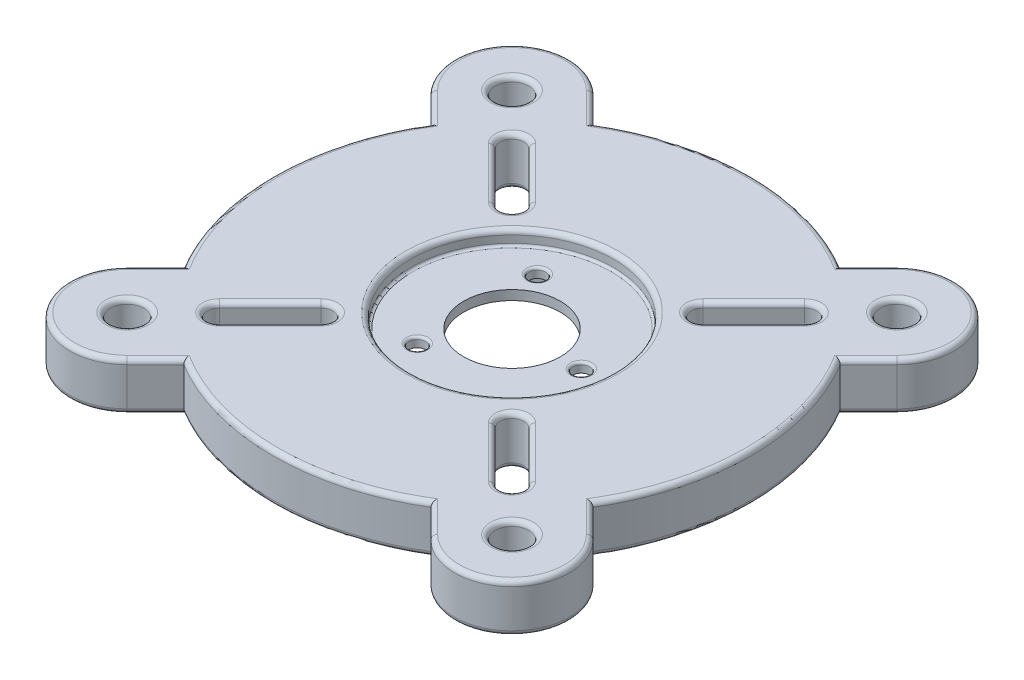
SolidWorks part; units mm, degrees
ref_plane "Front Plane" through (0, 0, 0) normal (0, 0, 1) x (1, 0, 0)
ref_plane "Top Plane" through (0, 0, 0) normal (0, 1, 0) x (1, 0, 0)
ref_plane "Right Plane" through (0, 0, 0) normal (1, 0, 0) x (0, 0, -1)
sketch "Sketch1" plane through (0, 0, 0) normal (0, 1, 0) x (1, 0, 0)
  line L0 (0, 0) -> (0, 28636.0271) construction
  line L1 (0, 0) -> (-28636.0271, 0) construction
  line L2 (-40.2487, -40.2487) -> (40.2487, 40.2487) construction
  line L3 (-48.734, -31.7635) -> (31.7635, 48.734)
  line L4 (-31.7635, -48.734) -> (48.734, 31.7635)
  line L5 (-40.2042, 40.2042) -> (40.2042, -40.2042) construction
  line L6 (-31.7189, 48.6895) -> (48.6895, -31.7189)
  line L7 (-48.6895, 31.7189) -> (31.7189, -48.6895)
  line L8 (20, 20) -> (30.6066, 30.6066) construction
  line L9 (18.2322, 21.7678) -> (28.8388, 32.3744)
  line L10 (21.7678, 18.2322) -> (32.3744, 28.8388)
  line L11 (20, -20) -> (30.6066, -30.6066) construction
  line L12 (21.7678, -18.2322) -> (32.3744, -28.8388)
  line L13 (18.2322, -21.7678) -> (28.8388, -32.3744)
  line L14 (-20, -20) -> (-30.6066, -30.6066) construction
  line L15 (-18.2322, -21.7678) -> (-28.8388, -32.3744)
  line L16 (-21.7678, -18.2322) -> (-32.3744, -28.8388)
  line L17 (-20, 20) -> (-30.6066, 30.6066) construction
  line L18 (-21.7678, 18.2322) -> (-32.3744, 28.8388)
  line L19 (-18.2322, 21.7678) -> (-28.8388, 32.3744)
  circle A0 centre (0, 0) radius 50
  arc A1 (-48.734, -31.7635) -> (-31.7635, -48.734) centre (-40.2487, -40.2487) ccw
  arc A2 (48.734, 31.7635) -> (31.7635, 48.734) centre (40.2487, 40.2487) ccw
  arc A3 (-31.7189, 48.6895) -> (-48.6895, 31.7189) centre (-40.2042, 40.2042) ccw
  arc A4 (31.7189, -48.6895) -> (48.6895, -31.7189) centre (40.2042, -40.2042) ccw
  arc A5 (48.734, 31.7635) -> (46.2093, 19.0972) centre (56.9581, 23.5394) ccw
  arc A6 (31.8511, 48.8208) -> (18.9141, 46.2845) centre (23.4535, 57.3928) cw
  circle A7 centre (40.2487, 40.2487) radius 3.5
  arc A8 (18.2322, 21.7678) -> (21.7678, 18.2322) centre (20, 20) ccw
  arc A9 (32.3744, 28.8388) -> (28.8388, 32.3744) centre (30.6066, 30.6066) ccw
  arc A10 (31.7635, -48.734) -> (19.0972, -46.2093) centre (23.5394, -56.9581) ccw
  circle A11 centre (40.2487, -40.2487) radius 3.5
  arc A12 (48.8208, -31.8511) -> (46.2845, -18.9141) centre (57.3928, -23.4535) cw
  arc A13 (21.7678, -18.2322) -> (18.2322, -21.7678) centre (20, -20) ccw
  arc A14 (28.8388, -32.3744) -> (32.3744, -28.8388) centre (30.6066, -30.6066) ccw
  arc A15 (-48.734, -31.7635) -> (-46.2093, -19.0972) centre (-56.9581, -23.5394) ccw
  circle A16 centre (-40.2487, -40.2487) radius 3.5
  arc A17 (-31.8511, -48.8208) -> (-18.9141, -46.2845) centre (-23.4535, -57.3928) cw
  arc A18 (-18.2322, -21.7678) -> (-21.7678, -18.2322) centre (-20, -20) ccw
  arc A19 (-32.3744, -28.8388) -> (-28.8388, -32.3744) centre (-30.6066, -30.6066) ccw
  arc A20 (-31.7635, 48.734) -> (-19.0972, 46.2093) centre (-23.5394, 56.9581) ccw
  circle A21 centre (-40.2487, 40.2487) radius 3.5
  arc A22 (-48.8208, 31.8511) -> (-46.2845, 18.9141) centre (-57.3928, 23.4535) cw
  arc A23 (-21.7678, 18.2322) -> (-18.2322, 21.7678) centre (-20, 20) ccw
  arc A24 (-28.8388, 32.3744) -> (-32.3744, 28.8388) centre (-30.6066, 30.6066) ccw
  point P9 (0, 0)
  point P16 (0, 0)
  point P30 (25.3033, 25.3033)
  point P48 (25.3033, -25.3033)
  point P63 (-25.3033, -25.3033)
  point P78 (-25.3033, 25.3033)
  dimension "D1" = 100
  dimension "D3" = 12
  dimension "D4" = 7
  dimension "D6" = 2.5
  dimension "D2" = 45
  dimension "D5" = 45
  dimension "D7" = 20
  dimension "D8" = 15
  dimension "D9" = 4
extrude "Boss-Extrude1" add sketch "Sketch1" along normal blind 10 contours L4 A0 L7 | L7 A0 L3 | L3 A0 L6 | L6 A0 L4 | L7 A0 L6 L4 A14 L13 A13 L12 | L7 A4 L6 A0 A11 | L3 L7 L4 L6 | L4 A0 L3 L6 A9 L10 A8 L9 | L4 A2 L3 A0 A7 | L6 A0 L7 L3 A24 L19 A23 L18 | L3 A0 L4 L7 A19 L16 A18 L15 | L3 A1 L4 A0 A16 | A3 L7 A4 L6 | L18 A24 L19 A23 | L12 A14 L13 A13 | A21 | A11 region at (-45.5065, 0, 29.0642) region at (-37.345, 0, 0) region at (-29.4609, 0, 13.3464) region at (-29.4609, 0, -13.3464) region at (0, 0, 0) region at (0, 0, 37.345) region at (0, 0, -37.345) region at (13.3464, 0, -29.4609) region at (8.9134, 0, 8.9134) region at (29.0642, 0, -45.5065) region at (37.345, 0, 0) region at (35.619, 0, 35.619)
sketch "Sketch2" plane through (0, 10, 0) normal (0, 1, 0) x (1, 0, 0)
  circle A0 centre (0, 0) radius 21.25
  circle A1 centre (14.5, 0) radius 1.75
  circle A2 centre (-7.25, -12.5574) radius 1.75
  circle A3 centre (-7.25, 12.5574) radius 1.75
  dimension "D1" = 42.5
  dimension "D2" = 3.5
  dimension "D3" = 14.5
  dimension "D4" = 3
extrude "Cut-Extrude1" cut sketch "Sketch2" against normal through all both and the other way through all contours A1 | A3 | A2 region at (14.5, 10, 0) region at (-7.25, 10, -12.5574)
extrude "Cut-Extrude2" cut sketch "Sketch2<3>" against normal blind 3
sketch "Sketch2<3>" plane through (0, 10, 0) normal (0, 1, 0) x (1, 0, 0) same geometry as "Sketch2"
fillet "Fillet1" radius 1 37 edges at (28.8001, 10, -45.7707) (48.734, 10, -48.734) (45.7707, 10, -28.8001) (50, 10, 0) (45.7484, 10, 28.7778) (48.6895, 10, 48.6895) (28.7778, 10, 45.7484) (0, 10, 50) (-28.8001, 10, 45.7707) (-48.734, 10, 48.734) (-45.7707, 10, 28.8001) (-50, 10, 0) (-45.7484, 10, -28.7778) (-48.6895, 10, -48.6895) (-28.7778, 10, -45.7484) (0, 10, -50) (-40.2487, 10, -36.7487) (-23.5355, 10, 27.0711) (-18.2322, 10, 18.2322) (-27.0711, 10, 23.5355) (-32.3744, 10, 32.3744) (-40.2487, 10, 43.7487) (-27.0711, 10, -23.5355) (-18.2322, 10, -18.2322) (-23.5355, 10, -27.0711) (-32.3744, 10, -32.3744) (27.0711, 10, 23.5355) (18.2322, 10, 18.2322) (23.5355, 10, 27.0711) (32.3744, 10, 32.3744) (40.2487, 10, 43.7487) (40.2487, 10, -36.7487) (23.5355, 10, -27.0711) (18.2322, 10, -18.2322) (27.0711, 10, -23.5355) (32.3744, 10, -32.3744) (0, 10, 21.25)
fillet "Fillet2" radius 1 39 edges at (-40.2487, 0, -36.7487) (-27.0711, 0, 23.5355) (-18.2322, 0, 18.2322) (-23.5355, 0, 27.0711) (-32.3744, 0, 32.3744) (-40.2487, 0, 43.7487) (-23.5355, 0, -27.0711) (-18.2322, 0, -18.2322) (-27.0711, 0, -23.5355) (-32.3744, 0, -32.3744) (23.5355, 0, 27.0711) (18.2322, 0, 18.2322) (27.0711, 0, 23.5355) (32.3744, 0, 32.3744) (40.2487, 0, 43.7487) (40.2487, 0, -36.7487) (27.0711, 0, -23.5355) (18.2322, 0, -18.2322) (23.5355, 0, -27.0711) (32.3744, 0, -32.3744) (45.7707, 0, -28.8001) (48.734, 0, -48.734) (28.8001, 0, -45.7707) (0, 0, -50) (-28.7778, 0, -45.7484) (-48.6895, 0, -48.6895) (-45.7484, 0, -28.7778) (-50, 0, 0) (-45.7707, 0, 28.8001) (-48.734, 0, 48.734) (-28.8001, 0, 45.7707) (0, 0, 50) (28.7778, 0, 45.7484) (48.6895, 0, 48.6895) (45.7484, 0, 28.7778) (50, 0, 0) (-7.25, 0, 14.3074) (-7.25, 0, -10.8074) (14.5, 0, 1.75)
fillet "Fillet3" radius 0.5 4 edges at (0, 7, 21.25) (14.5, 7, 1.75) (-7.25, 7, 14.3074) (-7.25, 7, -10.8074)
sketch "Sketch4" plane through (0, 0, 0) normal (0, -1, 0) x (1, 0, 0)
  circle A0 centre (0, 0) radius 21.25
  circle A1 centre (-7.25, -12.5574) radius 1.75
  circle A2 centre (14.5, 0) radius 1.75
  circle A3 centre (-7.25, 12.5574) radius 1.75
  dimension "D1" = 42.5
extrude "Cut-Extrude3" cut sketch "Sketch4" against normal blind 5
sketch "Sketch5" plane through (0, 5, 0) normal (0, -1, 0) x (1, 0, 0)
  circle A0 centre (0, 0) radius 10.1
extrude "Cut-Extrude4" cut sketch "Sketch5" against normal blind 5
